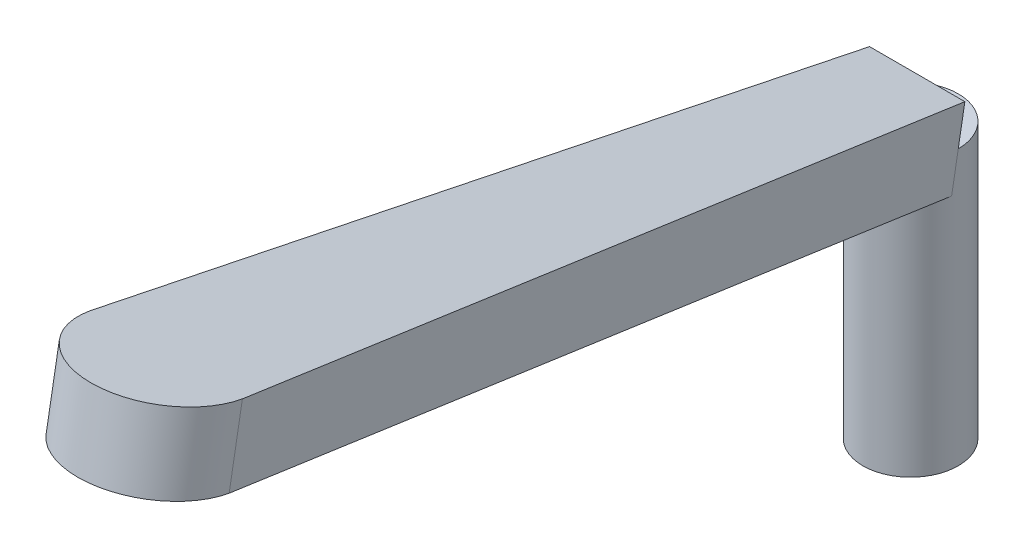
SolidWorks part; units mm, degrees
ref_plane "Front Plane" through (0, 0, 0) normal (0, 0, 1) x (1, 0, 0)
ref_plane "Top Plane" through (0, 0, 0) normal (0, 1, 0) x (1, 0, 0)
ref_plane "Right Plane" through (0, 0, 0) normal (1, 0, 0) x (0, 0, -1)
sketch "Sketch1" plane through (0, 0, 0) normal (0, 1, 0) x (1, 0, 0)
  circle A0 centre (0, 0) radius 7.9375
  dimension "D1" = 15.875
extrude "Boss-Extrude1" add sketch "Sketch1" along normal blind 45.72
ref_axis "Axis1" through (-8.7312, 45.72, 0) along (1, 0, 0)
ref_plane "Plane1" through (0, 44.3414, -7.8186) normal (0, -0.9848, 0.1736) x (1, 0, 0)
sketch "Sketch2" plane through (0, 44.3414, -7.8186) normal (0, -0.9848, 0.1736) x (1, 0, 0)
  line L0 (-8.7312, 7.9392) -> (8.7312, 7.9392) construction
  line L1 (-7.9375, 7.9392) -> (7.9375, 7.9392)
  line L2 (7.9375, 7.9392) -> (12.7, 134.9392)
  line L4 (-12.7, 134.9392) -> (-7.9375, 7.9392)
  arc A0 (-12.7, 134.9392) -> (12.7, 134.9392) centre (0, 134.9392) cw
  dimension "D2" = 12.7
  dimension "D1" = 127
extrude "Boss-Extrude2" add sketch "Sketch2" along normal mid plane 12.7
ref_axis "Axis2" through (0, -7.4496, 0) along (0, 1, 0)
